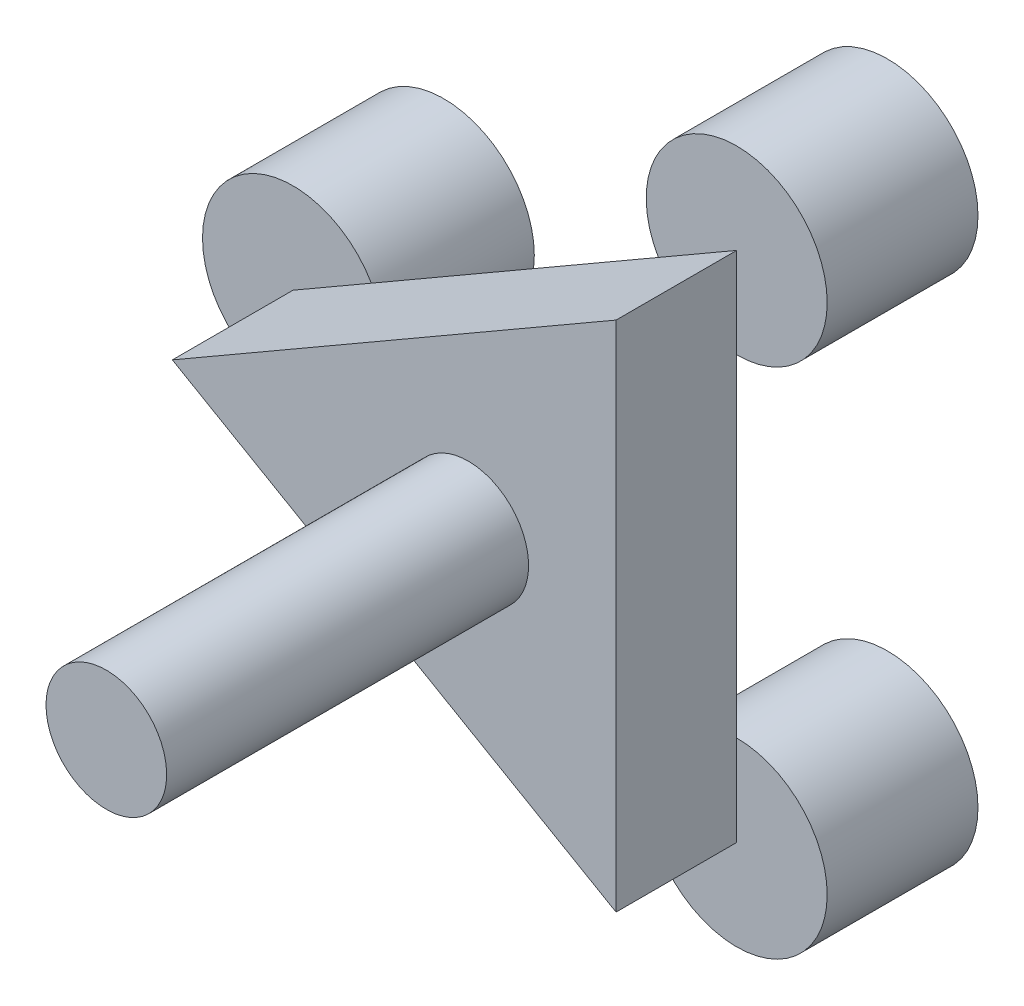
SolidWorks part; units mm, degrees
ref_plane "Front Plane" through (0, 0, 0) normal (0, 0, 1) x (1, 0, 0)
ref_plane "Top Plane" through (0, 0, 0) normal (0, 1, 0) x (1, 0, 0)
ref_plane "Right Plane" through (0, 0, 0) normal (1, 0, 0) x (0, 0, -1)
sketch "Sketch1" plane through (0, 0, 0) normal (0, 0, 1) x (1, 0, 0)
  line L0 (-46.7047, 0.009) -> (46.7064, -53.9728)
  line L1 (46.7064, -53.9728) -> (46.7064, 53.9728)
  line L2 (46.7064, 53.9728) -> (-46.7047, 0.009)
  circle A0 centre (46.7064, -53.9728) radius 19.05
  circle A1 centre (-46.7047, 0.009) radius 19.0517
  circle A2 centre (46.7064, 53.9728) radius 19.05
extrude "Boss-Extrude3" add sketch "Sketch1" against normal blind 31.75 contours L2 A1 L0 | L0 A1 L2 | L2 A2 L1 | L1 A2 L2 | L1 A0 L0 | L0 A0 L1 region at (-34.5768, 0.0081, 0) region at (-49.1322, 0.0092, 0) region at (40.6445, -43.4683, 0) region at (47.9182, -56.0727, 0) region at (47.9185, 56.0729, 0) region at (40.6438, 43.4689, 0)
extrude "Boss-Extrude4" add sketch "Sketch1<6>" along normal blind 25.4 contours A2 L2 A1 L0 A0 L1 | L0 A1 L2 | L1 A0 L0 | L2 A2 L1 region at (-34.5768, 0.0081, 0) region at (15.5716, 0.0028, 0) region at (40.6445, -43.4683, 0) region at (40.6438, 43.4689, 0)
sketch "Sketch1<6>" plane through (0, 0, 0) normal (0, 0, 1) x (1, 0, 0) same geometry as "Sketch1"
sketch "Sketch3" plane through (0, 0, 25.4) normal (0, 0, 1) x (1, 0, 0)
  circle A0 centre (15.5935, 0) radius 12.7
extrude "Boss-Extrude5" add sketch "Sketch3" along normal blind 76.2
